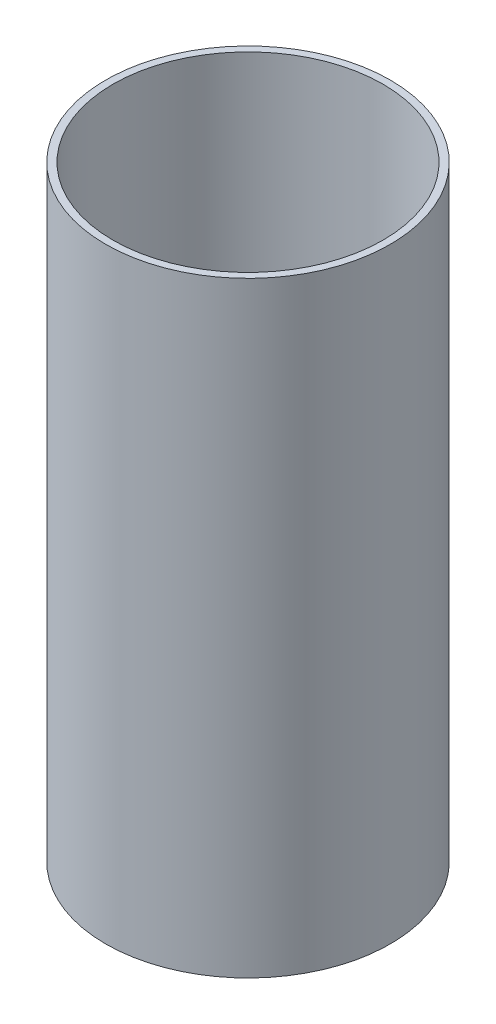
SolidWorks part; units mm, degrees
material "PVC Rigid"
ref_plane "Front Plane" through (0, 0, 0) normal (0, 0, 1) x (1, 0, 0)
ref_plane "Top Plane" through (0, 0, 0) normal (0, 1, 0) x (1, 0, 0)
ref_plane "Right Plane" through (0, 0, 0) normal (1, 0, 0) x (0, 0, -1)
sketch "Sketch1" plane through (0, 0, 0) normal (0, 1, 0) x (1, 0, 0)
  circle A0 centre (0, 0) radius 93.6625
  circle A1 centre (0, 0) radius 88.9
  dimension "D1" = 187.325
  dimension "D2" = 177.8
extrude "Boss-Extrude1" add sketch "Sketch1" along normal mid plane 398.78
ref_plane "Plane1" through (0, 0, 93.6625) normal (0, 0, 1) x (1, 0, 0)
sketch "Sketch3" plane through (0, 0, 93.6625) normal (0, 0, 1) x (1, 0, 0)
  line L0 (0, -55) -> (0, 55) construction
  line L1 (-93.6625, -199.39) -> (93.6625, -199.39) construction
  circle A0 centre (0, -193.04) radius 1.4351
  dimension "D1" = 2.8702
  dimension "D2" = 6.35
extrude "Cut-Extrude1" [suppressed] cut sketch "Sketch3" against normal blind 19.304
pattern_circular "CirPattern1" [suppressed] count 12 over 360 reverse direction yes of bodies 102
mirror "Mirror1" [suppressed] about plane through (0, 0, 0) normal (0, 1, 0)
sketch "Sketch4" [suppressed] plane through (0, 0, 93.6625) normal (0, 0, 1) x (1, 0, 0)
  line L0 (0, -103.0288) -> (0, 103.0288) construction
  circle A0 centre (0, 64.3636) radius 1.4351
  circle A1 centre (0, -64.3636) radius 1.4351
  circle A2 centre (0, 193.04) radius 1.4351 construction
  circle A3 centre (0, -193.04) radius 1.4351 construction
  dimension "D1" = 128.6764
  dimension "D2" = 128.6764
  dimension "D3" = 2.8702
  dimension "D4" = 2.8702
extrude "Cut-Extrude2" [suppressed] cut sketch "Sketch4" against normal blind 43.18
pattern_circular "CirPattern2" [suppressed] count 3 over 360 of bodies 105
